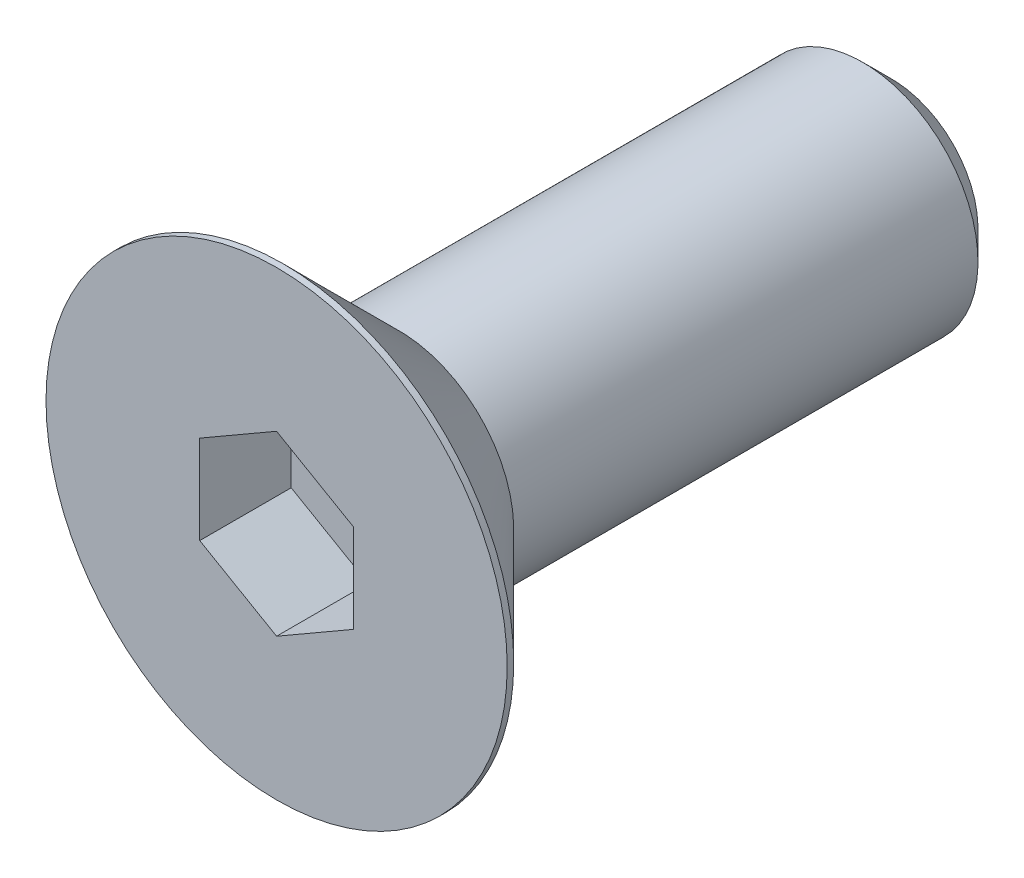
SolidWorks part; units mm, degrees
material "Chrome Stainless Steel"
ref_plane "Front" through (0, 0, 0) normal (0, 0, 1) x (1, 0, 0)
ref_plane "Top" through (0, 0, 0) normal (0, 1, 0) x (1, 0, 0)
ref_plane "Right" through (0, 0, 0) normal (1, 0, 0) x (0, 0, -1)
sketch "Sketch11" plane through (0, 0, 0) normal (1, 0, 0) x (0, 0, -1)
  line L0 (-4, 3) -> (4, 3) construction
  line L5 (-4, 3) -> (-4, -3) construction
  line L6 (4, 1.5) -> (4, -1.5) construction
  line L7 (-3.99, 1) -> (-3.99, -1) construction
  line L8 (3.9688, 1.5541) -> (4.4688, 1.5541) construction
  line L9 (4.4688, 1.5541) -> (4.2188, 1.1211) construction
  line L10 (4.2188, 1.1211) -> (3.9688, 1.5541) construction
  line L11 (4.1875, 1.1752) -> (4.25, 1.1752) construction
  line L12 (4.2188, 1.1752) -> (4.2188, 1.1211) construction
  line L13 (3.9844, 1.5271) -> (4.4531, 1.5271) construction
  line L14 (4.2188, 1.5541) -> (4.2188, 1.5) construction
  line L15 (4, 1.5) -> (4.4375, 1.5) construction
  line L17 (-3.915, 3) -> (-0.915, 0) construction
  line L18 (-0.915, 0) -> (-3.915, -3) construction
  point P3 (-2.3, 3)
  point P8 (0, 3)
  point P21 (4.2188, 1.5271)
  point P26 (-4, 0)
  point P28 (-3.99, 0)
  point P29 (4, 0)
  dimension "Length" = 8
  dimension "Head Diameter" = 6
  dimension "Thread Major Diameter" = 3
  dimension "Head Height" = 1.7
  dimension "Drive Size" = 2
  dimension "Thread Pitch" = 0.5
  dimension "D1" = 0.0625
  dimension "D2" = 0.01
  dimension "D3" = 0.085
  dimension "Countersink Angle" = 90
sketch "Sketch1" plane through (0, 0, 0) normal (1, 0, 0) x (0, 0, -1)
  line L2 (-2.3, 1.5) -> (4, 1.5)
  line L3 (4, 1.5) -> (4, 0)
  line L4 (-2.81, 1.5) -> (-2.81, 0)
  line L5 (-2.3, 1.5) -> (-2.81, 1.5)
  line L6 (-4, 3) -> (-4, -3) construction
  line L7 (4, 1.5) -> (4, -1.5) construction
  line L8 (-2.81, 0) -> (4, 0)
  dimension "D1" = 1.19
revolve "Revolve1" add sketch "Sketch1" angle 360 mid plane about L8
chamfer "Chamfer1" distance 0.375 angle 45 1 edges at (0, -1.5, -4)
sketch "Sketch7" plane through (0, 0, 0) normal (1, 0, 0) x (0, 0, -1)
  line L2 (-4, 3) -> (-3.915, 3)
  line L5 (-2.3, 1.385) -> (-2.3, 0)
  line L6 (-4, 3) -> (-4, 0)
  line L8 (-4, 3) -> (-4, -3) construction
  line L9 (-4, 0) -> (-2.3, 0)
  line L12 (-3.915, 3) -> (-2.3, 1.385)
  line L13 (-3.915, 3) -> (-0.915, 0) construction
revolve "Revolve2" add sketch "Sketch7" angle 360 mid plane about L9 region at (0, 1.1696, 3.2571)
ref_plane "Plane1" through (0, 0, 2.3) normal (0, 0, 1) x (1, 0, 0)
sketch "Sketch5" plane through (0, 0, 4) normal (0, 0, 1) x (1, 0, 0)
  line L1 (1, -0.5774) -> (1, 0.5774)
  line L2 (1, 0.5774) -> (0, 1.1547)
  line L3 (0, 1.1547) -> (-1, 0.5774)
  line L4 (-1, 0.5774) -> (-1, -0.5774)
  line L5 (-1, -0.5774) -> (0, -1.1547)
  line L6 (0, -1.1547) -> (1, -0.5774)
  circle A0 centre (0, 0) radius 1 construction
extrude "Cut-Extrude2" cut sketch "Sketch5" against normal blind 1.19
sketch "Sketch6" plane through (0, 0, 4) normal (0, 0, -1) x (-1, 0, 0)
  circle A0 centre (0, 0) radius 1.1547
extrude "Cut-Extrude3" [suppressed] cut sketch "Sketch6" along normal blind 1.19 draft 45
sketch "Sketch12" [suppressed] plane through (0, 0, -4) normal (0, 0, -1) x (-1, 0, 0)
  circle A0 centre (0, 0) radius 1.5 construction
  circle A1 centre (0, 0) radius 1.5
curve "Helix/Spiral1" [suppressed] pitch 0.5 height 8 turns 16
sketch "Sketch13" [suppressed] plane through (0, 0, 0) normal (1, 0, 0) x (0, 0, -1)
  line L0 (3.9844, 1.5271) -> (4.4531, 1.5271)
  line L1 (4.4531, 1.5271) -> (4.25, 1.1752)
  line L2 (4.25, 1.1752) -> (4.1875, 1.1752)
  line L3 (4.1875, 1.1752) -> (3.9844, 1.5271)
sweep "Cut-Sweep1" [suppressed] cut profiles "Sketch13" path "Helix/Spiral1"
combine bodies "Combine1" [suppressed] operation type add bodies to combine 113 127
equation "\"D1@Chamfer1\"=\"Thread Pitch@Sketch11\" * .75"
equation "\"D1@Cut-Extrude2\"= \"Head Height@Sketch11\" * .7"
equation "\"D1@Cut-Extrude3\" = \"D1@Cut-Extrude2\""
equation "\"D1@Sketch11\"=\"Thread Pitch@Sketch11\"/8"
equation "\"D3@Sketch11\"=\"Head Height@Sketch11\"*.05"
equation "\"D4@Helix/Spiral1\"=\"Thread Pitch@Sketch11\""
equation "\"D1@Sketch1\"=\"Head Height@Sketch11\"*.7"
equation "\"D3@Helix/Spiral1\"=\"Length@Sketch11\""
